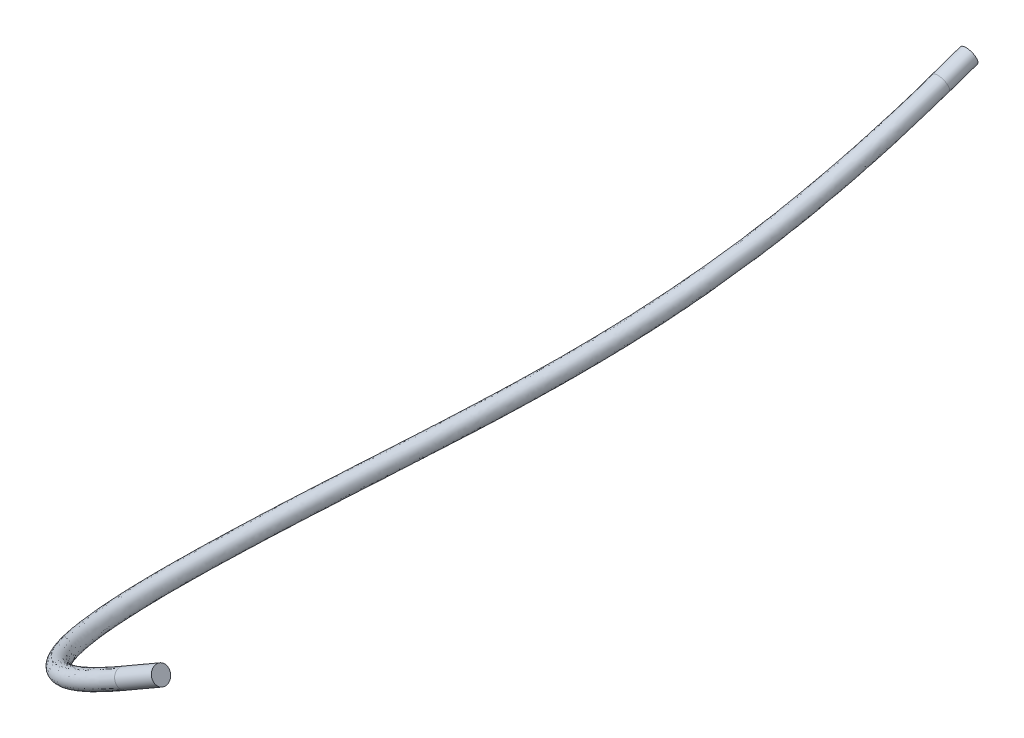
SolidWorks part; units mm, degrees
ref_plane "Front Plane" through (0, 0, 0) normal (0, 0, 1) x (1, 0, 0)
ref_plane "Top Plane" through (0, 0, 0) normal (0, 1, 0) x (1, 0, 0)
ref_plane "Right Plane" through (0, 0, 0) normal (1, 0, 0) x (0, 0, -1)
sketch "Sketch1" plane through (0, -41.4652, 119.8102) normal (0, -0.3271, 0.945) x (1, 0, 0)
  circle A0 centre (-87.9132, 33.3425) radius 1.905
  circle A1 centre (-87.9132, 33.3425) radius 1.905 construction
sketch3d "3DSketch1"
  line L0 (-66.7888, -18.0775, 330.1356) -> (-74.8986, -22.7597, 330.1356)
  line L1 (-87.9132, -9.9564, 130.7151) -> (-87.9132, -12.1163, 136.956)
  spline S0 degree 3 poles (-87.9132, -12.1163, 136.956) (-87.9132, -28.969, 185.6504) (-98.4063, -33.349, 243.4821) (-114.0138, -45.3429, 330.1356) (-74.8986, -22.7597, 330.1356) knots 0 0 0 0 0.534528 1 1 1 1
  point P3 (-30.9181, -217.9617, 340.1591)
  point P4 (33.1833, -200.0232, 255.8739)
  point P5 (33.1833, -35.8269, 201.5232)
  point P6 (-114.9858, -35.8269, 250.6306)
  point P7 (-100.5922, -35.8269, 255.7107)
  dimension "D1" = 6.604
sweep "Sweep1" add profiles "Sketch1" path "3DSketch1"
